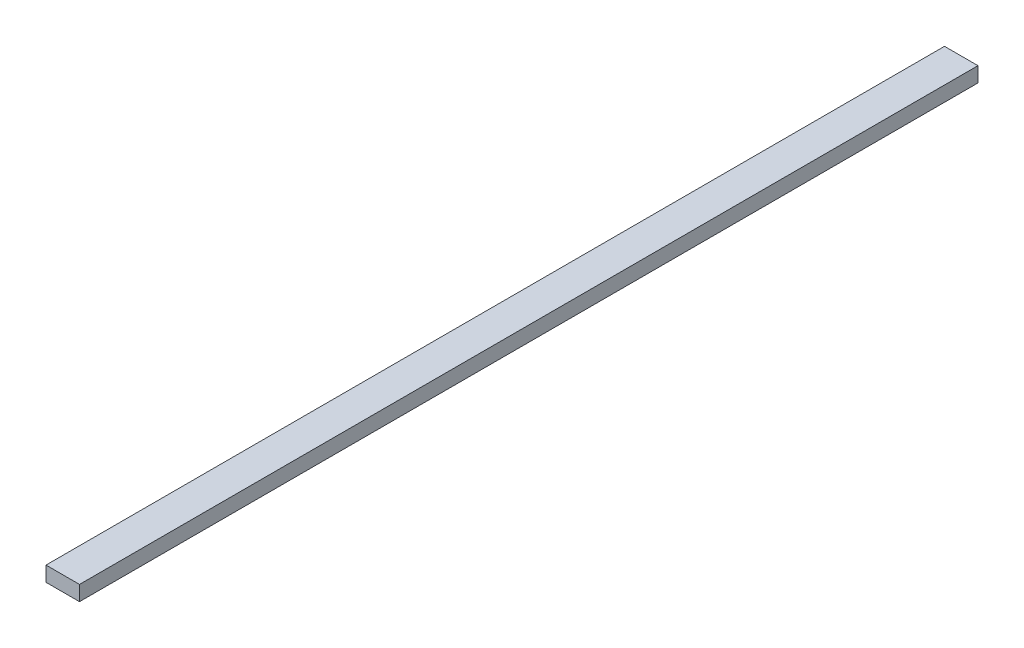
SolidWorks part; units mm, degrees
ref_plane "Front Plane" through (0, 0, 0) normal (1, 0, 0) x (0, 1, 0)
ref_plane "Top Plane" through (0, 0, 0) normal (0, 0, 1) x (0, 1, 0)
ref_plane "Right Plane" through (0, 0, 0) normal (0, 1, 0) x (-1, 0, 0)
sketch "Sketch1" plane through (0, 0, 0) normal (0, 0, 1) x (0, 1, 0)
  line L1 (-8.3312, -18.6436) -> (8.3312, -18.6436)
  line L2 (-8.3312, -18.6436) -> (-8.3312, 18.6436)
  line L3 (-8.3312, 18.6436) -> (8.3312, 18.6436)
  line L4 (8.3312, -18.6436) -> (8.3312, 18.6436)
  line L5 (-8.3312, -18.6436) -> (8.3312, 18.6436) construction
  line L6 (-8.3312, 18.6436) -> (8.3312, -18.6436) construction
  point P0 (0, 0)
  dimension "D1" = 16.6624
  dimension "D2" = 37.2872
extrude "Boss-Extrude1" add sketch "Sketch1" along normal mid plane 1000
